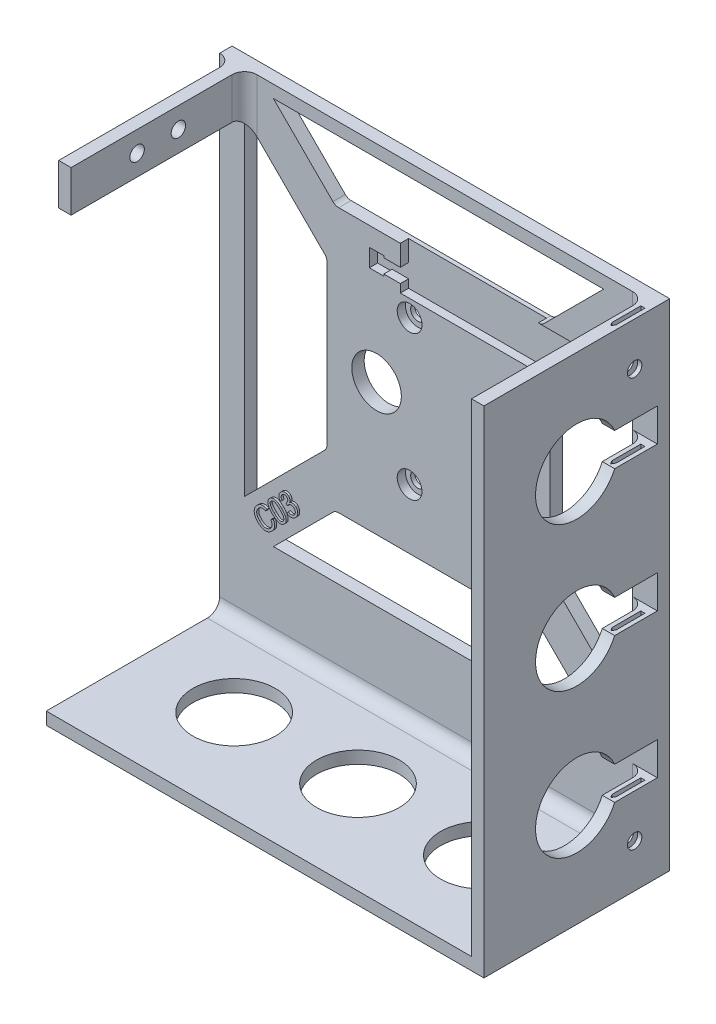
SolidWorks part; units mm, degrees
ref_plane "Front Plane" through (0, 0, 0) normal (0, 0, 1) x (1, 0, 0)
ref_plane "Top Plane" through (0, 0, 0) normal (0, 1, 0) x (1, 0, 0)
ref_plane "Right Plane" through (0, 0, 0) normal (1, 0, 0) x (0, 0, -1)
sketch "Sketch1" plane through (0, 0, 0) normal (0, 0, 1) x (1, 0, 0)
  line L1 (-50, 50) -> (50, 50)
  line L2 (-50, 50) -> (-50, -50)
  line L3 (-50, -50) -> (50, -50)
  line L4 (50, 50) -> (50, -50)
  line L5 (-50, 50) -> (50, -50) construction
  line L6 (-50, -50) -> (50, 50) construction
  line L7 (-47, 40) -> (-27, 20)
  line L8 (-27, 20) -> (-27, -20)
  line L9 (-27, -20) -> (-47, -40)
  line L11 (-47, 40) -> (-47, -40)
  line L12 (0, -50) -> (0, 50) construction
  line L13 (47, 40) -> (27, 20)
  line L14 (27, 20) -> (27, -20)
  line L15 (27, -20) -> (47, -40)
  line L16 (47, 40) -> (47, -40)
  line L17 (-40, 47) -> (40, 47)
  line L18 (40, 47) -> (25, 32)
  line L19 (25, 32) -> (-25, 32)
  line L20 (-25, 32) -> (-40, 47)
  line L21 (-50, 0) -> (50, 0) construction
  line L22 (25, -32) -> (-25, -32)
  line L23 (40, -47) -> (25, -32)
  line L24 (-40, -47) -> (40, -47)
  line L25 (-25, -32) -> (-40, -47)
  line L26 (50, -50) -> (50, -70)
  line L31 (50, 50) -> (53, 50)
  line L32 (50, 50) -> (50, -50)
  line L33 (50, -50) -> (53, -50)
  line L34 (53, 50) -> (53, -50)
  line L35 (-50, 50) -> (-53, 50)
  line L36 (-50, 50) -> (-50, -50)
  line L37 (-50, -50) -> (-53, -50)
  line L38 (-53, 50) -> (-53, -50)
  line L39 (-53, -50) -> (53, -50)
  line L40 (-53, -50) -> (-53, -70)
  line L41 (-53, -50) -> (53, -50)
  line L42 (-53, -70) -> (53, -70)
  line L43 (53, -50) -> (53, -70)
  circle A2 centre (-15, 0) radius 6
  circle A3 centre (-7, 17.5) radius 1.75
  circle A4 centre (-7, -17.5) radius 1.75
  point P0 (0, 0)
  point P6 (-47, 0)
  point P8 (-50, 0)
  point P23 (0, 47)
  dimension "D16" = 12
  dimension "D14" = 3.5
  dimension "D1" = 100
  dimension "D2" = 100
  dimension "D3" = 80
  dimension "D4" = 45
  dimension "D5" = 20
  dimension "D6" = 3
  dimension "D7" = 3
  dimension "D8" = 45
  dimension "D9" = 80
  dimension "D10" = 15
  dimension "D11" = 3
  dimension "D13" = 17.5
  dimension "D12" = 35
  dimension "D15" = 8
  dimension "D17" = 45
  dimension "D18" = 45
  dimension "D19" = 3
  dimension "D20" = 20
extrude "Base" add sketch "Sketch1" along normal blind 3 contours L1 L34 L16 L3 L4 | L40 L39 L43 L42 | L36 L35 L38 L37 | L32 L31 L34 L33 region at (0.3319, 0, 0)
sketch "Sketch6" plane through (0, 0, 3) normal (0, 0, 1) x (1, 0, 0)
  line L0 (40, 47) -> (47, 40) construction
  line L1 (-47, -40) -> (-40, -47) construction
  line L2 (-41.7678, -45.2322) -> (45.2322, 41.7678) construction
  line L3 (47, 40) -> (27, 20) construction
  text T0 "C03" font "Century Gothic" height 5
  dimension "D1" = 2.5
extrude "Revision" add sketch "Sketch6" along normal blind 0.5
sketch "Sketch3" plane through (0, 0, 3) normal (0, 0, 1) x (1, 0, 0)
  circle A0 centre (-7, 17.5) radius 3
  circle A1 centre (-7, -17.5) radius 3
  dimension "D1" = 6
  dimension "D2" = 6
extrude "Stepper_Holes" cut sketch "Sketch3" against normal blind 2
sketch "Sketch4" plane through (0, 0, 3) normal (0, 0, 1) x (1, 0, 0)
  line L0 (-15, 0) -> (-50.929, 0)
  line L1 (-50.929, 0) -> (-50.929, 40.2605)
  dimension "D1" = 35.929
  dimension "D2" = 40.2605
sketch "Sketch5" plane through (0, 0, 3) normal (0, 0, 1) x (1, 0, 0)
  line L0 (-50, 50) -> (-50, 40)
  line L2 (-50, 40) -> (-47, 40)
  line L6 (-47, 50) -> (-50, 50)
  line L7 (-47, 40) -> (-47, 50)
  line L8 (-53, 0) -> (0, 0) construction
  dimension "D1" = 10
  dimension "D2" = 3
extrude "Front_Tower" add sketch "Sketch5" along normal blind 42
sketch "Sketch8" plane through (-47, 0, 0) normal (1, 0, 0) x (0, 0, -1)
  line L1 (-45, 50) -> (-3, 50) construction
  line L2 (-24, 50) -> (-24, 40) construction
  line L3 (-45, 40) -> (-3, 40) construction
  circle A1 centre (-29, 45) radius 1.75
  circle A2 centre (-19, 45) radius 1.75
  point P13 (-24, 45)
  dimension "D1" = 3.5
  dimension "D2" = 5
extrude "Flip_Holder_Cut" cut sketch "Sketch8" against normal up to surface (3 mm away) up to face at (-50, 45, 24)
sketch "Sketch10" plane through (0, 0, 3) normal (0, 0, 1) x (1, 0, 0)
  line L7 (-53, -70) -> (53, -70)
  line L9 (53, -70) -> (53, 50)
  line L10 (53, 50) -> (50, 50)
  line L11 (-47, 50) -> (53, 50) construction
  line L12 (50, 50) -> (50, -67)
  line L13 (50, -67) -> (-53, -67)
  line L14 (-53, 50) -> (-53, -70) construction
  line L15 (-53, -67) -> (-53, -70)
  dimension "D1" = 3
extrude "Boss-Extrude1" add sketch "Sketch10" along normal blind 42
fillet "Fillet-2mm" radius 2 8 edges at (25, 32, 1.5) (-25, 32, 1.5) (-27, 20, 1.5) (27, 20, 1.5) (27, -20, 1.5) (-27, -20, 1.5) (25, -32, 1.5) (-25, -32, 1.5)
sketch "Sketch11" plane through (53, 0, 0) normal (1, 0, 0) x (0, 0, -1)
  line L0 (-13.3348, -14) -> (-3, -14)
  line L1 (-45, 50) -> (0, 50) construction
  line L2 (-45, -70) -> (-45, 50) construction
  line L3 (-3, -14) -> (-3, -6)
  line L4 (-3, -6) -> (-13.3348, -6)
  line L5 (0, 58.3) -> (0, -58.3) construction
  line L6 (-13.3348, 21) -> (-3, 21)
  line L7 (-3, 21) -> (-3, 29)
  line L8 (-3, 29) -> (-13.3348, 29)
  line L9 (-13.3348, -6) -> (-13.3348, 29) construction
  line L10 (-13.3348, -49) -> (-3, -49)
  line L11 (-3, -49) -> (-3, -41)
  line L12 (-3, -41) -> (-13.3348, -41)
  line L13 (-13.3348, -6) -> (-13.3348, -41) construction
  arc A0 (-13.3348, -6) -> (-13.3348, -14) centre (-22.5, -10) ccw
  arc A1 (-13.3348, 29) -> (-13.3348, 21) centre (-22.5, 25) ccw
  arc A2 (-13.3348, -41) -> (-13.3348, -49) centre (-22.5, -45) ccw
  point P5 (-22.5, 50)
  point P13 (-45, -10)
  point P17 (-3, -10)
  dimension "D1" = 2
  dimension "D4" = 20
  dimension "D5" = 35
  dimension "D2" = 35
  dimension "D3" = 2
  dimension "D6" = 3
  dimension "D7" = 8
  dimension "WireChannelLength" = 10.3348
extrude "Back_Cut" cut sketch "Sketch11" against normal up to surface (3 mm away) up to face at (50, -8.5, 24)
sketch "Sketch12" plane through (0, -70, 0) normal (0, -1, 0) x (1, 0, 0)
  line L0 (-53, 45) -> (53, 45) construction
  line L1 (53, 45) -> (53, 0) construction
  line L2 (-53, 45) -> (-53, 0) construction
  circle A0 centre (0, 22.5) radius 10
  circle A1 centre (-30, 22.5) radius 10
  circle A2 centre (30, 22.5) radius 10
  point P11 (0, 45)
  point P15 (53, 22.5)
  point P19 (-53, 22.5)
  dimension "D1" = 20
  dimension "D2" = 20
  dimension "D3" = 20
  dimension "D4" = 30
  dimension "D5" = 30
extrude "Bottom_Cut" cut sketch "Sketch12" against normal up to surface (3 mm away) up to face at (-1.5, -67, 24)
sketch "Sensor" plane through (0, 0, 3) normal (0, 0, 1) x (1, 0, 0)
  line L1 (-16.75, 23.1) -> (-13.25, 23.1)
  line L2 (-16.75, 23.1) -> (-16.75, 27.4)
  line L3 (-16.75, 27.4) -> (-13.25, 27.4)
  line L4 (-13.25, 23.1) -> (-13.25, 23.55)
  line L10 (-9.25, 26.95) -> (-9.25, 32)
  line L13 (-13.25, 26.95) -> (-9.25, 26.95)
  line L14 (47, 40) -> (27.5858, 20.5858) construction
  line L16 (-9.25, 23.55) -> (-13.25, 23.55)
  line L17 (-13.25, 26.95) -> (-13.25, 27.4)
  line L18 (-9.25, 32) -> (39, 32)
  line L20 (39, 32) -> (39, 21.55)
  line L21 (39, 21.55) -> (-9.25, 21.55)
  line L22 (-9.25, 21.55) -> (-9.25, 23.55)
  point P4 (-16.75, 25.25)
  point P6 (-15, 23.1)
  point P18 (0, 0)
  dimension "D1" = 3.5
  dimension "D2" = 4.3
  dimension "D3" = 3.4
  dimension "D4" = 4
  dimension "D5" = 2
  dimension "D6" = 25.25
extrude "Sensor_Cut" cut sketch "Sensor" against normal blind 2
sketch "Sketch16" plane through (0, 50, 0) normal (0, 1, 0) x (1, 0, 0)
  line L0 (51, -12) -> (51.5, -12.8)
  line L1 (52, -5) -> (51, -5)
  line L2 (52, -5) -> (52, -12)
  line L4 (51, -5) -> (51, -12)
  line L5 (51.5, -12.8) -> (52, -12)
  line L6 (-58.3, 0) -> (58.3, 0) construction
  line L7 (50, -45) -> (50, -3) construction
  line L8 (53, -45) -> (53, 0) construction
  dimension "D1" = 5
  dimension "D3" = 1
  dimension "D4" = 1
  dimension "D2" = 0.8
  dimension "D6" = 7
extrude "Wire_Channel_Cut" cut sketch "Sketch16" against normal up to surface (120 mm away) and the other way through all up to face at (30, -70, 12.5)
sketch "Sketch17" plane through (53, 0, 0) normal (1, 0, 0) x (0, 0, -1)
  line L0 (0, 58.3) -> (0, -58.3) construction
  line L3 (-8.5, -70) -> (-8.5, -49) construction
  line L4 (-45, -70) -> (0, -70) construction
  line L5 (-13.3348, -49) -> (-3, -49) construction
  line L6 (-8.5, 29) -> (-8.5, 50) construction
  line L7 (-3, 29) -> (-13.3348, 29) construction
  line L9 (-45, 50) -> (0, 50) construction
  line L10 (0, 50) -> (0, -70) construction
  circle A0 centre (-8.5, -59.5) radius 1.75
  circle A1 centre (-8.5, 39.5) radius 1.75
  point P2 (-8.5, -59.5)
  point P13 (-8.5, 39.5)
  dimension "D1" = 3.5
  dimension "D3" = 3.5
  dimension "D2" = 8.5
  dimension "D4" = 8.5
  dimension "D5" = 10.5
  dimension "D6" = 10.5
fillet "Fillet-0.5mm" [suppressed] radius 0.5
fillet "Fillet-3mm" radius 3 7 edges at (-50, 45, 3) (-47, 45, 3) (50, 39.5, 3) (-1.5, -67, 3) (50, 7.5, 3) (50, -27.5, 3) (50, -58, 3)
extrude "Wire_Holder_Screw_Holes" cut sketch "Sketch17" against normal up to surface (3 mm away) up to face at (50, -9.625, 17.219)
equation "\"D3@Sketch1\"=\"D2@Sketch1\"*.8"
equation "\"D9@Sketch1\"=\"D1@Sketch1\"*.8"
equation "\"ServoDriverBoard_Width\"= 26.6mm"
equation "\"ServoDriverBoard_Length\"= 29.6mm"
equation "\"ServoDriverBoard_FromTop\"= 5mm"
equation "\"ServoDriverBoard_HoleSize\"= 3.3mm"
equation "\"Frame Size\"= 100mm"
equation "\"D1@Sketch1\"=\"Frame Size\""
equation "\"D2@Sketch3\"=\"D1@Sketch3\""
equation "\"Flip Y Offset\"= 36 * sin ( 3.6 )"
equation "\"Flip X Position\"= 36 * cos ( 3.6 )"
equation "\"Flip Length\"= 38mm"
equation "\"D1@Sketch4\"=\"Flip X Position\""
equation "\"D2@Sketch4\"=\"Flip Y Offset\"+\"Flip Length\""
equation "\"D2@Sketch12\"=\"D1@Sketch12\""
equation "\"D3@Sketch12\"=\"D1@Sketch12\""
equation "\"D4@Sketch12\"=\"D5@Sketch12\""
equation "\"D4@Sketch16\"=\"D3@Sketch16\""
